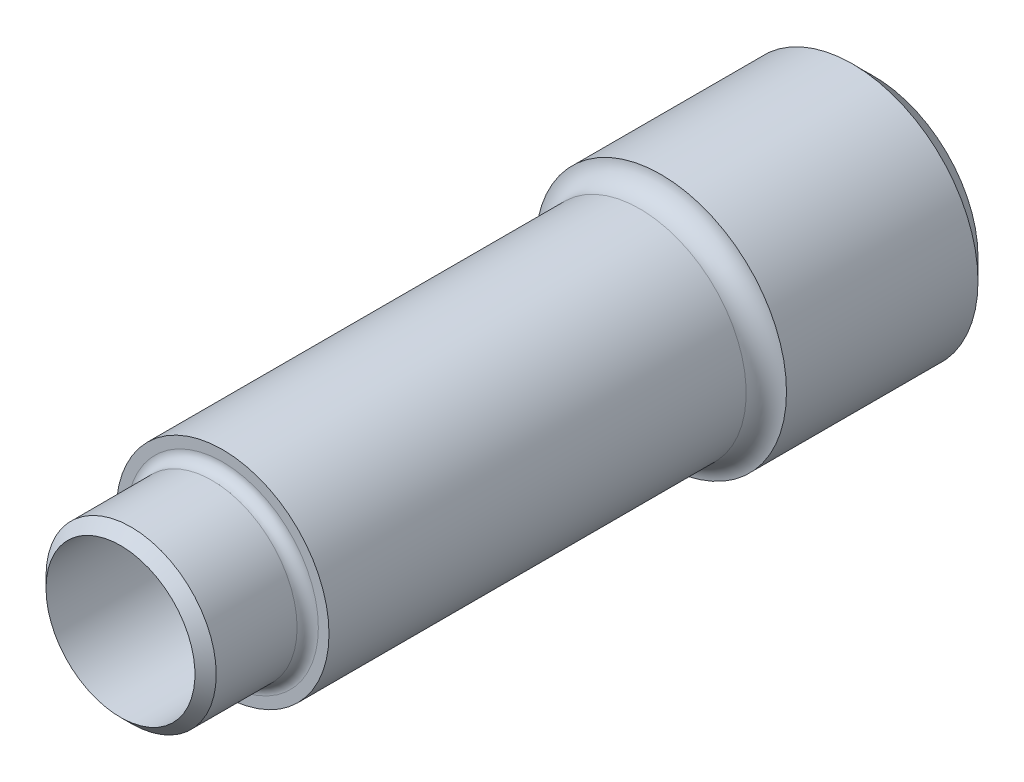
SolidWorks part; units mm, degrees
material "Plain Carbon Steel"
ref_plane "Front Plane" through (0, 0, 0) normal (0, 0, 1) x (1, 0, 0)
ref_plane "Top Plane" through (0, 0, 0) normal (0, 1, 0) x (1, 0, 0)
ref_plane "Right Plane" through (0, 0, 0) normal (1, 0, 0) x (0, 0, -1)
sketch "Sketch1" plane through (0, 0, 0) normal (0, 0, 1) x (1, 0, 0)
  circle A0 centre (0, 0) radius 12.7
  dimension "D1" = 25.4
extrude "Boss-Extrude1" add sketch "Sketch1" along normal blind 89.916
sketch "Sketch2" plane through (0, 0, 0) normal (0, 0, -1) x (-1, 0, 0)
  circle A0 centre (0, 0) radius 8.89
  circle A1 centre (0, 0) radius 12.7 construction
  dimension "D1" = 3.81
extrude "Cut-Extrude1" cut sketch "Sketch2" against normal through all
sketch "Sketch3" plane through (0, 0, 0) normal (0, 0, -1) x (-1, 0, 0)
  circle A0 centre (0, 0) radius 10.033
  circle A1 centre (0, 0) radius 12.7 construction
  dimension "D1" = 2.667
extrude "Cut-Extrude2" cut sketch "Sketch3" against normal blind 12.7
sketch "Sketch4" plane through (0, 0, 89.916) normal (0, 0, 1) x (1, 0, 0)
  circle A0 centre (0, 0) radius 10.16
  circle A1 centre (0, 0) radius 12.7 construction
  circle A2 centre (0, 0) radius 12.7
  dimension "D1" = 2.54
extrude "Cut-Extrude3" cut sketch "Sketch4" against normal blind 12.192
fillet "Fillet1" radius 1.27 1 edges at (10.16, 0, 77.724)
chamfer "Chamfer1" distance 1.27 angle 45 1 edges at (-10.033, 0, 0)
fillet "Fillet2" radius 0.635 1 edges at (-10.033, 0, 12.7)
chamfer "Chamfer2" distance 1.27 angle 45 1 edges at (10.16, 0, 89.916)
sketch "Sketch5" plane through (0, 0, 0) normal (0, 0, -1) x (-1, 0, 0)
  circle A0 centre (0, 0) radius 14.986
  circle A1 centre (0, 0) radius 12.7
  circle A2 centre (0, 0) radius 12.7 construction
  dimension "D1" = 29.972
extrude "Boss-Extrude2" add sketch "Sketch5" against normal blind 25.4
fillet "Fillet3" radius 2.54 1 edges at (-12.7, 0, 25.4)
chamfer "Chamfer3" distance 2.54 angle 45 1 edges at (-14.986, 0, 0)
